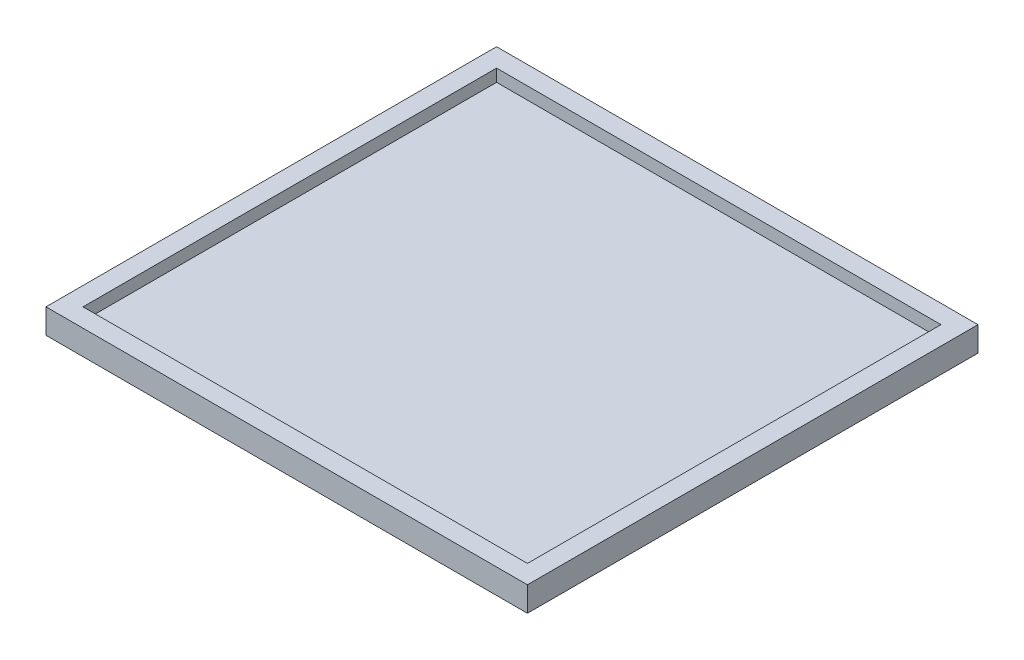
SolidWorks part; units mm, degrees
ref_plane "Front Plane" through (0, 0, 0) normal (0, 0, 1) x (1, 0, 0)
ref_plane "Top Plane" through (0, 0, 0) normal (0, 1, 0) x (1, 0, 0)
ref_plane "Right Plane" through (0, 0, 0) normal (1, 0, 0) x (0, 0, -1)
sketch "Sketch2" plane through (0, 0, 0) normal (0, 1, 0) x (1, 0, 0)
  line L1 (0, 0) -> (78, 0)
  line L2 (0, 0) -> (0, 73)
  line L3 (0, 73) -> (78, 73)
  line L4 (78, 0) -> (78, 73)
  dimension "D1" = 78
  dimension "D2" = 73
extrude "Boss-Extrude1" add sketch "Sketch2" along normal blind 4
sketch "Sketch3" plane through (0, 4, 0) normal (0, 1, 0) x (1, 0, 0)
  line L0 (78, 73) -> (0, 73) construction
  line L1 (3, 70) -> (75, 70)
  line L2 (3, 70) -> (3, 3)
  line L3 (3, 3) -> (75, 3)
  line L4 (75, 70) -> (75, 3)
  line L5 (78, 0) -> (78, 73) construction
  line L6 (0, 0) -> (78, 0) construction
  line L7 (0, 73) -> (0, 0) construction
  dimension "D1" = 3
  dimension "D2" = 3
  dimension "D3" = 3
  dimension "D4" = 3
extrude "Cut-Extrude1" cut sketch "Sketch3" against normal blind 2 contours L3 L4 L1 L2
